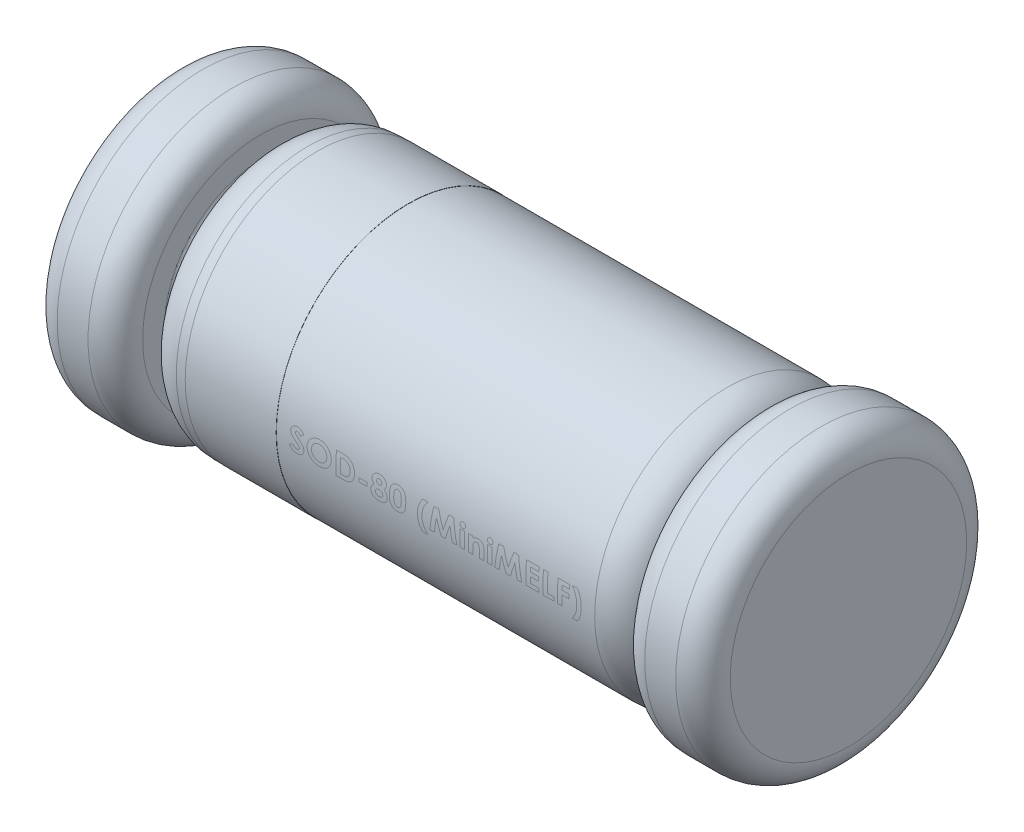
SolidWorks part; units mm, degrees
ref_plane "Ön Düzlem" through (0, 0, 0) normal (0, 0, 1) x (1, 0, 0)
ref_plane "Üst Düzlem" through (0, 0, 0) normal (0, 1, 0) x (1, 0, 0)
ref_plane "Sağ Düzlem" through (0, 0, 0) normal (1, 0, 0) x (0, 0, -1)
sketch "Çizim1" plane through (0, 0, 0) normal (1, 0, 0) x (0, 0, 1)
  circle A0 centre (0.8, 0) radius 0.8
  dimension "D1" = 1.6
sketch "Çizim2" plane through (0, 0, 0) normal (1, 0, 0) x (0, 0, -1)
  circle A2 centre (-0.8, 0) radius 0.725
  dimension "D2" = 1.45
extrude "Yükseklik-Ekstrüzyon3" add sketch "Çizim2" along normal mid plane 2.7
fillet "Radyus1" radius 0.2 2 edges at (-1.35, 0, 0.075) (1.35, 0, 0.075)
extrude "Ekstrüzyon-İnce1" add sketch "Çizim2<2>" against normal blind 0.5 from offset 0.6 thin offset against normal yes thin type one direction wall 0.001
sketch "Çizim2<2>" plane through (0, 0, 0) normal (1, 0, 0) x (0, 0, -1) same geometry as "Çizim2"
sketch "Çizim3" plane through (0, 0, 0) normal (-1, 0, 0) x (0, 0, 1)
  circle A2 centre (0.8, 0) radius 0.5
  dimension "D1" = 1
extrude "Yükseklik-Ekstrüzyon6" add sketch "Çizim3" along normal blind 0.06 from offset 1.35
extrude "Yükseklik-Ekstrüzyon2" add sketch "Çizim1" against normal blind 0.47 from offset 1.41 offset against normal yes
extrude "Yükseklik-Ekstrüzyon7" add sketch "Çizim1<3>" along normal blind 0.47 from offset 1.35
sketch "Çizim1<3>" plane through (0, 0, 0) normal (1, 0, 0) x (0, 0, 1) same geometry as "Çizim1"
fillet "Radyus2" radius 0.15 4 edges at (1.35, 0, 0) (1.82, 0, 0) (-1.41, 0, 0) (-1.88, 0, 0)
fillet "Radyus3" radius 0.03 1 edges at (-1.41, 0, 1.3)
ref_plane "Düzlem1" through (0, 0, 1) normal (0, 0, 1) x (1, 0, 0)
sketch "Çizim4" plane through (0, 0, 1) normal (0, 0, 1) x (1, 0, 0)
  line L0 (-0.5842, 0.3572) -> (1.1534, 0.3572) construction
  text T1 "\r\n\r\n<b> SOD-80 (MiniMELF)</b>\r\n\r\n" font "Century Gothic" height 0.12
wrap "Sar1" sketch "Çizim4" wrap type scribe source sketch "Çizim4" face at (-0.6, 0, 0.075)
